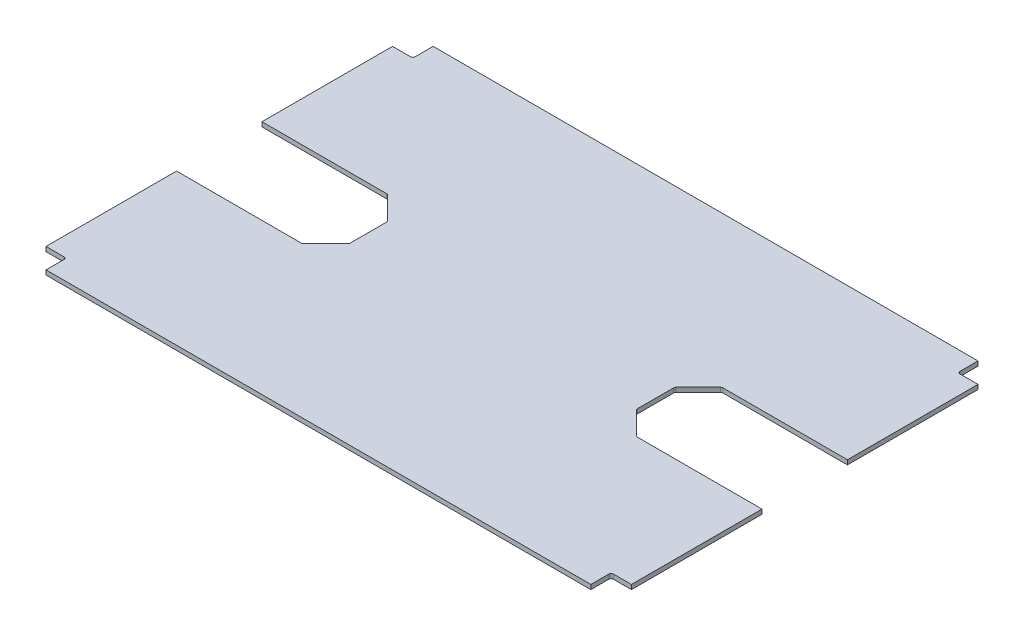
SolidWorks part; units mm, degrees
material "Mahogany"
ref_plane "Front Plane" through (0, 0, 0) normal (0, 0, 1) x (1, 0, 0)
ref_plane "Top Plane" through (0, 0, 0) normal (0, 1, 0) x (1, 0, 0)
ref_plane "Right Plane" through (0, 0, 0) normal (1, 0, 0) x (0, 0, -1)
sketch "Sketch1" plane through (0, 0, 0) normal (0, 1, 0) x (1, 0, 0)
  line L0 (-620, 90.5) -> (-304, 90.5)
  line L1 (-620, 410) -> (620, 410)
  line L2 (-620, 410) -> (-620, -410)
  line L3 (-620, -410) -> (620, -410)
  line L4 (620, 410) -> (620, -410)
  line L5 (-620, 410) -> (620, -410) construction
  line L6 (-620, -410) -> (620, 410) construction
  line L7 (-620, 410) -> (-577, 410)
  line L8 (-620, 410) -> (-620, 367)
  line L9 (-620, 367) -> (-577, 367)
  line L10 (-577, 410) -> (-577, 367)
  line L11 (620, 410) -> (577, 410)
  line L12 (620, 410) -> (620, 367)
  line L13 (620, 367) -> (577, 367)
  line L14 (577, 410) -> (577, 367)
  line L15 (620, -410) -> (577, -410)
  line L16 (620, -410) -> (620, -367)
  line L17 (620, -367) -> (577, -367)
  line L18 (577, -410) -> (577, -367)
  line L19 (-620, -410) -> (-577, -410)
  line L20 (-620, -410) -> (-620, -367)
  line L21 (-620, -367) -> (-577, -367)
  line L22 (-577, -410) -> (-577, -367)
  line L23 (-304, 90.5) -> (-304, -90.5)
  line L24 (-304, -90.5) -> (-620, -90.5)
  line L25 (620, 90.5) -> (304, 90.5)
  line L26 (304, 90.5) -> (304, -90.5)
  line L27 (304, -90.5) -> (620, -90.5)
  point P0 (0, 0)
  point P26 (304, 0)
  point P27 (-304, 0)
  dimension "D1" = 1240
  dimension "D2" = 820
  dimension "D3" = 43
  dimension "D4" = 316
  dimension "D5" = 181
extrude "Boss-Extrude1" add sketch "Sketch1" along normal blind 9.525 contours L27 L26 L25 L4 L13 L14 L1 L10 L9 L2 L0 L23 L24 L21 L22 L3 L18 L17 region at (0, 0, 0)
chamfer "Chamfer1" distance 50 angle 45 4 edges at (304, 4.7625, 90.5) (304, 4.7625, -90.5) (-304, 4.7625, 90.5) (-304, 4.7625, -90.5)
fillet "Fillet2" radius 5 12 edges at (577, 4.7625, -367) (577, 4.7625, 367) (-577, 4.7625, 367) (-577, 4.7625, -367) (304, 4.7625, -40.5) (304, 4.7625, 40.5) (354, 4.7625, 90.5) (354, 4.7625, -90.5) (-354, 4.7625, 90.5) (-304, 4.7625, 40.5) (-304, 4.7625, -40.5) (-354, 4.7625, -90.5)
equation "\"W\"= 1200"
equation "\"L\"= 780"
equation "\"H\"= 780"
equation "\"ARM_BOLT_SPACING\"= 166"
equation "\"ARM_TO_WALL\"= 120"
equation "\"D1@Sketch1\"=\"W\"+40"
equation "\"D2@Sketch1\"=\"L\"+40"
equation "\"D4@Sketch1\"=\"ARM_TO_WALL\"+\"ARM_BOLT_SPACING\"+30"
equation "\"D5@Sketch1\"=\"ARM_BOLT_SPACING\"+15"
